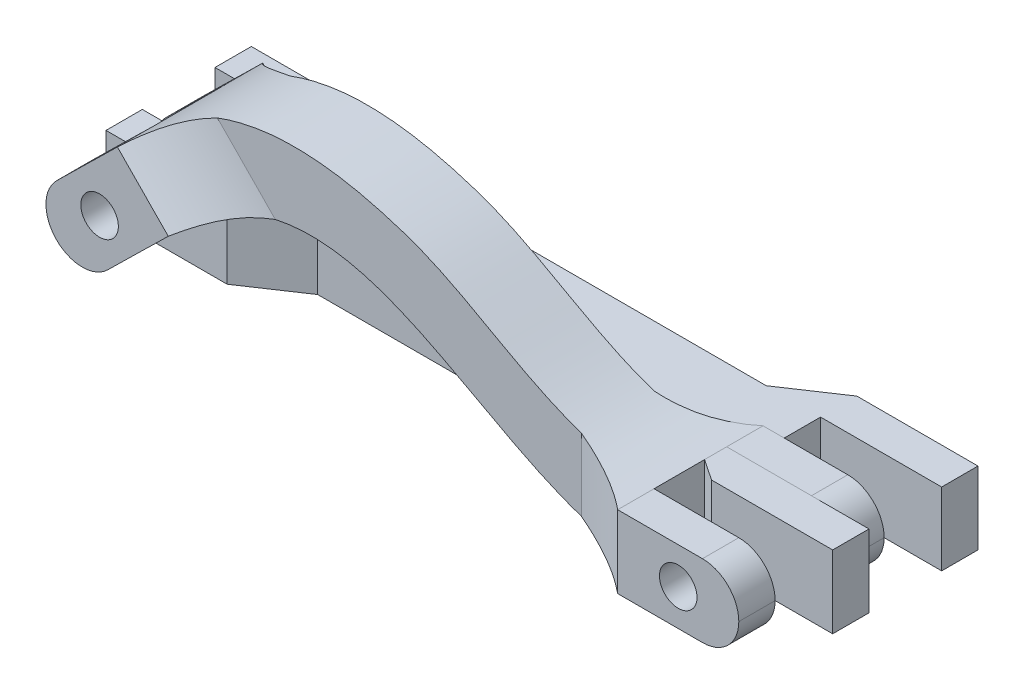
SolidWorks part; units mm, degrees
ref_plane "Front Plane" through (0, 0, 0) normal (0, 0, 1) x (1, 0, 0)
ref_plane "Top Plane" through (0, 0, 0) normal (0, 1, 0) x (1, 0, 0)
ref_plane "Right Plane" through (0, 0, 0) normal (1, 0, 0) x (0, 0, -1)
sketch "Sketch1" plane through (0, 0, 0) normal (0, 1, 0) x (1, 0, 0)
  line L0 (0, -3) -> (0, 3)
  line L1 (0, -3) -> (-15.5181, -3)
  line L4 (-20, -3) -> (-20, 3)
  line L5 (20, 6) -> (15.5181, 3)
  line L6 (30, 3) -> (30, 6)
  line L7 (-20, 3) -> (-30, 3)
  line L9 (-20, 6) -> (-30, 6)
  line L10 (-30, 3) -> (-30, 6)
  line L23 (20, 6) -> (30, 6)
  line L26 (-20, 6) -> (-15.5181, 3)
  line L27 (-15.5181, 3) -> (15.5181, 3)
  line L28 (-20, 0) -> (20, 0) construction
  line L29 (20, 3) -> (30, 3)
  line L30 (20, -3) -> (20, 3)
  line L31 (20, -3) -> (30, -3)
  line L32 (-15.5181, -3) -> (15.5181, -3)
  line L33 (-20, -6) -> (-15.5181, -3)
  line L34 (20, -6) -> (30, -6)
  line L35 (-30, -3) -> (-30, -6)
  line L36 (-20, -6) -> (-30, -6)
  line L37 (-20, -3) -> (-30, -3)
  line L38 (30, -3) -> (30, -6)
  line L39 (20, -6) -> (15.5181, -3)
  line L40 (0, 3) -> (-15.5181, 3)
  point P0 (0, 0)
  point P3 (0, 0)
  point P21 (0, 0)
  dimension "D1" = 3
  dimension "D2" = 10
  dimension "D4" = 20
extrude "Boss-Extrude1" add sketch "Sketch1" along normal blind 6 contours L10 L7 L26 L9 | L5 | L4 L1 | L32 | L30 region at (-15.2437, 0, 0) region at (15.2437, 0, 0)
sketch "Sketch2" [suppressed] plane through (0, 0, -6) normal (0, 0, -1) x (-1, 0, 0)
  line L0 (20, 6) -> (30, 0) construction
  line L1 (30, 0) -> (30, 6) construction
  line L2 (30, 6) -> (20, 0) construction
  circle A0 centre (25, 3) radius 1.6
  dimension "D1" = 3.2
extrude "Cut-Extrude1" [suppressed] cut sketch "Sketch2" against normal through all
mirror "Mirror1" [suppressed] about plane through (0, 0, 0) normal (1, 0, 0)
fillet "Fillet1" [suppressed] radius 3
sketch "Sketch3" [suppressed] plane through (0, 0, 0) normal (0, 1, 0) x (1, 0, 0)
  line L0 (29.9765, -6.9701) -> (29.9765, -3.9701)
  line L1 (29.9765, -3.9701) -> (19.9765, -3.9701)
  line L2 (19.9765, -3.9701) -> (19.9765, 2.0299)
  line L3 (19.9765, 2.0299) -> (29.9765, 2.0299)
  line L4 (29.9765, 2.0299) -> (29.9765, 5.0299)
  line L5 (29.9765, 5.0299) -> (19.9765, 5.0299)
  line L6 (19.9765, 5.0299) -> (15.4965, 2.0299)
  line L7 (29.9765, -6.9701) -> (19.9765, -6.9701)
  line L8 (19.9765, -6.9701) -> (15.4965, -3.9701)
  line L13 (-28.1862, -7.3241) -> (-30.3022, -5.1975)
  line L14 (-30.3022, -5.1975) -> (-23.2135, 1.8558)
  line L15 (-23.2135, 1.8558) -> (-27.4455, 6.1091)
  line L16 (-27.4455, 6.1091) -> (-34.5342, -0.9443)
  line L17 (-34.5342, -0.9443) -> (-36.6502, 1.1823)
  line L18 (-36.6502, 1.1823) -> (-29.5615, 8.2357)
  line L19 (-29.5615, 8.2357) -> (-24.2556, 9.2831)
  line L20 (-28.1862, -7.3241) -> (-21.0974, -0.2708)
  line L21 (-21.0974, -0.2708) -> (-20.0235, 5.0299)
  spline S0 degree 3 poles (-20.0235, 5.0299) (-3.0951, 14.6403) (0.5397, -11.3521) (15.4965, -3.9701) knots 0 0 0 0 1 1 1 1
  spline S1 degree 3 poles (-24.2556, 9.2831) (-15.7269, 13.0123) (-1.2248, 13.8312) (7.3682, -2.8075) (15.4965, 2.0299) knots 0 0 0 0 0.449578 1 1 1 1
  point P21 (0, 8.0991)
  point P22 (6.2924, 3)
  point P23 (7.2269, 2.1213)
  point P24 (-5.2333, 11.8995)
  point P26 (-6.417, 12.3356)
  point P28 (0, 0)
  point P38 (7.1646, 3)
  point P40 (7.1646, 3)
  point P41 (-5.2, 11.9379)
  point P43 (-24.2351, 10.2174)
  point P44 (-20, 6)
  point P46 (-2.1805, 3)
  point P47 (6.1055, -3)
  point P49 (19.9765, -0.9701)
  point P50 (0, 0)
  point P52 (-2.2428, 3)
  point P53 (0, 0)
  point P56 (-24.2426, 10.2555)
  dimension "D8" = 1.65
  dimension "D11" = 3
  dimension "D20" = 44
  dimension "D21" = 5.9
  dimension "D1" = 4.5
  dimension "D2" = 6
  dimension "D3" = 10
  dimension "D4" = 3
  dimension "D5" = 4.5
  dimension "D6" = 3
  dimension "D7" = 3
  dimension "D10" = 14.8
  dimension "D12" = 9.5
  dimension "D13" = 8.35
  dimension "D14" = 40
  dimension "D15" = 10
  dimension "D16" = 20
  dimension "D17" = 6
  dimension "D18" = 4.48
  dimension "D19" = 4.48
  dimension "D22" = 17.75
  dimension "D23" = 8.9
  dimension "D24" = 6.35
extrude "Boss-Extrude2" [suppressed] add sketch "Sketch3" along normal blind 6 separate body
fillet "Fillet2" [suppressed] radius 12.5
fillet "Fillet3" [suppressed] radius 5
fillet "Fillet4" [suppressed] radius 3
ref_plane "Plane1" [suppressed] through (-12.4766, 0, -12.5391) normal (-0.7053, 0, -0.7089) x (-0.7089, 0, 0.7053)
sketch "Sketch4" [suppressed] plane through (-12.4766, 0, -12.5391) normal (-0.7053, 0, -0.7089) x (-0.7089, 0, 0.7053)
  line L0 (15.1464, 6) -> (22.1464, 6) construction
  line L1 (15.1464, 6) -> (15.1464, 0) construction
  circle A0 centre (20.1464, 3) radius 1.55
  dimension "D1" = 3.1
  dimension "D2" = 3
  dimension "D3" = 5
extrude "Cut-Extrude2" [suppressed] cut sketch "Sketch4" against normal through all both and the other way through all
fillet "Fillet5" [suppressed] radius 55
sketch "Sketch5" [suppressed] plane through (0, 0, 0) normal (0, 0, 1) x (1, 0, 0)
  line L0 (19.9765, 6) -> (19.9765, 0) construction
  line L1 (19.9765, 6) -> (26.9765, 6) construction
  circle A0 centre (24.9765, 3) radius 1.55
  dimension "D1" = 3.1
  dimension "D2" = 5
  dimension "D3" = 3
extrude "Cut-Extrude3" [suppressed] cut sketch "Sketch5" against normal through all both and the other way through all
sketch "Sketch6" plane through (0, 0, 0) normal (0, 0, 1) x (1, 0, 0)
  line L1 (-26, 0) -> (-30.2, 4.2849)
  line L2 (-30.2, 4.2849) -> (-23.0586, 11.2849)
  line L3 (-26, 0) -> (-18.8586, 7)
  line L4 (18.25, 0) -> (28.25, 0)
  line L5 (28.25, 0) -> (28.25, 6)
  line L6 (28.25, 6) -> (18.25, 6)
  spline S0 degree 3 poles (18.25, 0) (5.0457, -0.0601) (-4.9293, 16.503) (-18.8586, 7) knots 0 0 0 0 1 1 1 1
  spline S1 degree 3 poles (-23.0586, 11.2849) (-16.2806, 17.2976) (-6.4303, 15.4016) (4.6219, 11.5239) (10.5597, 5.9825) (18.25, 6) knots 0 0 0 0 0.365109 0.440505 1 1 1 1
  point P2 (0, 0)
  point P12 (7.7093, 8.752)
  point P14 (-5.4279, 13.9218)
  point P16 (9.8381, 7.3623)
  point P18 (2.2355, 11.6106)
  point P19 (9.2907, 8.1438)
  point P20 (-1.9612, 14.7124)
  point P21 (-1.9003, 13.8001)
  point P23 (0, 0)
  dimension "D5" = 18.25
  dimension "D2" = 26
  dimension "D3" = 6
  dimension "D4" = 10
  dimension "D6" = 4
  dimension "D7" = 4.9
  dimension "D8" = 4.35
  dimension "D9" = 9.45
  dimension "D10" = 7
  dimension "D11" = 2.2
  dimension "D12" = 9
  dimension "D13" = 11.15
  dimension "D14" = 5.6
extrude "Boss-Extrude3" add sketch "Sketch6" along normal blind 12 separate body
sketch "Sketch7" plane through (0, 0, 0) normal (0, 1, 0) x (1, 0, 0)
  line L0 (12.25, -3) -> (-6.75, -3)
  line L1 (-6.75, -9) -> (12.25, -9)
  line L3 (18.25, -12) -> (18.25, 0) construction
  line L6 (-6.75, -3) -> (-6.75, 2.7213)
  line L7 (-6.75, 2.7213) -> (-31.75, 2.7213)
  line L8 (-31.75, 2.7213) -> (-31.75, -14.7213)
  line L9 (-31.75, -14.7213) -> (-6.75, -14.7213)
  line L10 (-6.75, -14.7213) -> (-6.75, -9)
  line L11 (18.25, -12) -> (28.25, -12)
  line L12 (28.25, -12) -> (28.25, 0)
  line L13 (28.25, 0) -> (18.25, 0)
  arc A0 (18.25, 0) -> (12.25, -3) centre (8.7117, 11.5767) cw
  arc A3 (12.25, -9) -> (18.25, -12) centre (8.7117, -23.5767) cw
  point P4 (-17.0583, -14.9217)
  point P15 (0, 0)
  point P22 (-1.7342, -14.7213)
  dimension "D3" = 15
  dimension "D5" = 25
  dimension "D4" = 17.4426
  dimension "D1" = 6
  dimension "D2" = 6
  dimension "D6" = 19
extrude "Cut-Extrude4" cut sketch "Sketch7" along normal through all both and the other way through all flip side to cut
ref_plane "Plane2" through (-16.94, 17.2823, 0) normal (-0.7, 0.7141, 0) x (0.7141, 0.7, 0)
sketch "Sketch8" plane through (-16.94, 17.2823, 0) normal (-0.7, 0.7141, 0) x (0.7141, 0.7, 0)
  line L0 (-18.5677, 0) -> (-8.5677, 0)
  line L1 (-18.5677, 0) -> (-18.5677, -12)
  line L2 (-18.5677, -12) -> (-8.5677, -12)
  line L3 (-8.5677, -12) -> (-8.5677, 0) construction
  line L4 (-2.5677, -3) -> (8.1336, -3)
  line L8 (8.1336, -9) -> (-2.5677, -9)
  line L9 (8.1336, -9) -> (8.1336, -13.6673)
  line L10 (8.1336, -13.6673) -> (26.3019, -13.6673)
  line L11 (26.3019, -13.6673) -> (26.3019, 1.6673)
  line L12 (26.3019, 1.6673) -> (8.1336, 1.6673)
  line L13 (8.1336, 1.6673) -> (8.1336, -3)
  line L14 (5.7734, -9) -> (13.6433, -9) construction
  arc A0 (-8.5677, 0) -> (-2.5677, -3) centre (0.9706, 11.5767) ccw
  arc A1 (-8.5677, -12) -> (-2.5677, -9) centre (0.9706, -23.5767) cw
  point P14 (8.1336, -9)
  dimension "D2" = 15
  dimension "D3" = 15.3347
  dimension "D1" = 6
  dimension "D4" = 18.1683
  dimension "D5" = 10.7013
extrude "Cut-Extrude5" cut sketch "Sketch8" against normal through all both and the other way through all flip side to cut
sketch "Sketch9" plane through (-16.94, 17.2823, 0) normal (-0.7, 0.7141, 0) x (0.7141, 0.7, 0)
  line L0 (-18.5677, -12) -> (-18.5677, 0) construction
  line L1 (-18.5677, -9) -> (-8.5677, -9)
  line L2 (-18.5677, -9) -> (-18.5677, -3)
  line L3 (-18.5677, -3) -> (-8.5677, -3)
  line L4 (-8.5677, -9) -> (-8.5677, -3)
  line L5 (-8.5677, -12) -> (-18.5677, -12) construction
  dimension "D1" = 6
  dimension "D2" = 10
  dimension "D3" = 3
extrude "Cut-Extrude6" cut sketch "Sketch9" against normal through all both and the other way through all
sketch "Sketch11" plane through (0, 0, 0) normal (0, 1, 0) x (1, 0, 0)
  line L0 (18.25, -12) -> (18.25, 0) construction
  line L1 (18.25, -9) -> (28.25, -9)
  line L2 (18.25, -9) -> (18.25, -3)
  line L3 (18.25, -3) -> (28.25, -3)
  line L4 (28.25, -9) -> (28.25, -3)
  line L5 (28.25, -12) -> (28.25, 0) construction
  line L6 (28.25, 0) -> (18.25, 0) construction
  line L7 (28.25, -12) -> (18.25, -12) construction
  dimension "D1" = 3
  dimension "D2" = 3
extrude "Cut-Extrude7" cut sketch "Sketch11" along normal through all both and the other way through all
fillet "Fillet6" radius 3 8 edges at (28.25, 6, 10.5) (28.25, 0, 10.5) (28.25, 0, 1.5) (28.25, 6, 1.5) (-26, 0, 10.5) (-30.2, 4.2849, 10.5) (-26, 0, 1.5) (-30.2, 4.2849, 1.5)
sketch "Sketch12" plane through (0, 0, 0) normal (0, 0, 1) x (1, 0, 0)
  line L0 (-18.8586, 7) -> (-23.0586, 11.2849) construction
  line L1 (-23.8576, 2.1) -> (-18.8586, 7) construction
  line L2 (18.25, 0) -> (18.25, 6) construction
  line L3 (25.25, 6) -> (18.25, 6) construction
  circle A0 centre (-24.5293, 5.6424) radius 1.55
  circle A1 centre (23.25, 3) radius 1.55
  point P6 (0, 0)
  point P8 (0, 0)
  dimension "D1" = 3.1
  dimension "D2" = 3.1
  dimension "D3" = 5
  dimension "D4" = 3
  dimension "D5" = 5
  dimension "D6" = 3
extrude "Cut-Extrude8" cut sketch "Sketch12" along normal through all both and the other way through all
